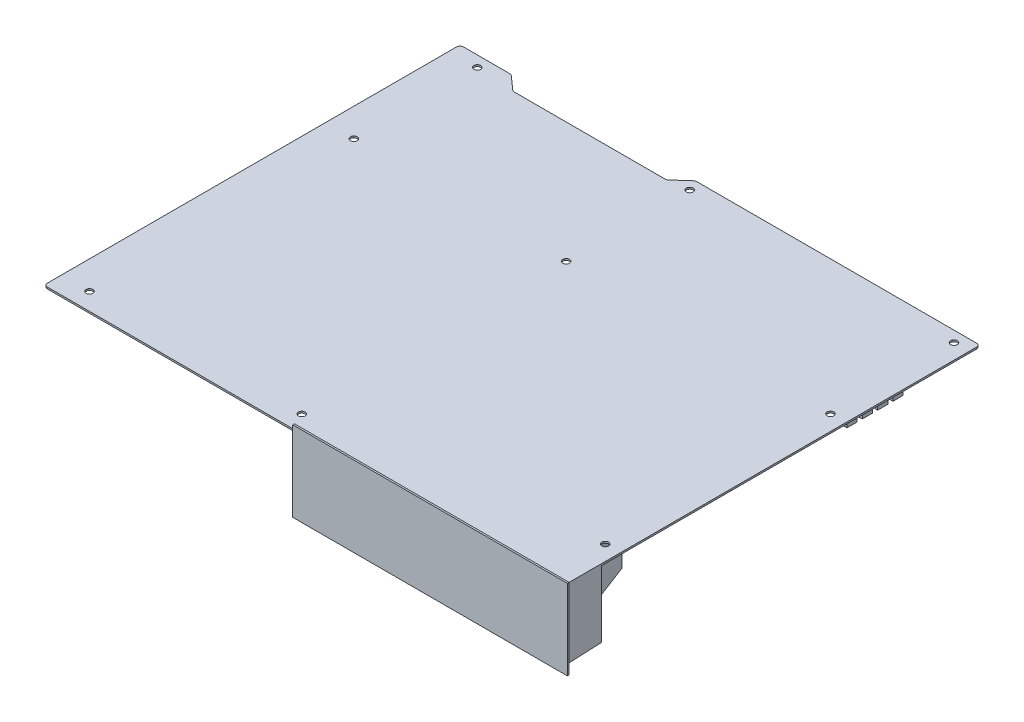
SolidWorks part; units mm, degrees
ref_plane "Front" through (0, 0, 0) normal (0, 0, 1) x (1, 0, 0)
ref_plane "Top" through (0, 0, 0) normal (0, 1, 0) x (1, 0, 0)
ref_plane "Right" through (0, 0, 0) normal (1, 0, 0) x (0, 0, -1)
sketch "Sketch1" plane through (0, 0, 0) normal (0, 1, 0) x (1, 0, 0)
  line L0 (-122.4, 121.92) -> (-122.4, 113.92) construction
  line L2 (-152.4, 121.92) -> (-152.4, -121.92)
  line L3 (-152.4, -121.92) -> (152.4, -121.92)
  line L4 (152.4, 121.92) -> (152.4, -121.92)
  line L7 (-122.4, 113.92) -> (-14.4, 113.92) construction
  line L8 (-14.4, 113.92) -> (-14.4, 121.92) construction
  line L9 (-152.4, 121.92) -> (-122.4, 121.92)
  line L10 (-14.4, 121.92) -> (152.4, 121.92)
  line L11 (-113.4, 113.92) -> (-23.4, 113.92)
  line L12 (-113.4, 113.92) -> (-122.4, 121.92)
  line L13 (-23.4, 113.92) -> (-14.4, 121.92)
  line L14 (-152.4, -111.76) -> (152.4, -111.76) construction
  line L15 (-152.4, 43.18) -> (152.4, 43.18) construction
  line L16 (-152.4, 115.57) -> (152.4, 115.57) construction
  line L17 (-135.89, -121.92) -> (-135.89, 121.92) construction
  line L18 (-11.43, -121.92) -> (-11.43, 115.57) construction
  line L19 (143.51, -121.92) -> (143.51, 121.92) construction
  circle A0 centre (-11.43, -111.76) radius 1.9812
  circle A1 centre (143.51, -88.9) radius 1.9812
  circle A2 centre (-135.89, 43.18) radius 1.9812
  circle A3 centre (-11.43, 115.57) radius 1.9812
  circle A4 centre (-135.89, 115.57) radius 1.9812
  circle A5 centre (143.51, 115.57) radius 1.9812
  circle A6 centre (-135.89, -111.76) radius 1.9812
  circle A7 centre (143.51, 43.18) radius 1.9812
  circle A8 centre (-11.43, 43.18) radius 1.9812
  point P0 (0, 0)
  point P12 (-68.4, 113.92)
  point P13 (-68.4, 113.92)
  dimension "D13" = 3.9624
  dimension "D1" = 304.8
  dimension "D2" = 243.84
  dimension "D3" = 30
  dimension "D4" = 108
  dimension "D5" = 90
  dimension "D6" = 8
  dimension "D7" = 227.33
  dimension "D8" = 10.16
  dimension "D9" = 154.94
  dimension "D10" = 124.46
  dimension "D11" = 279.4
  dimension "D12" = 16.51
  dimension "D14" = 22.86
extrude "Boss-Extrude1" add sketch "Sketch1" along normal blind 1
fillet "Fillet1" radius 2 4 edges at (-14.4, 0.5, -121.92) (-23.4, 0.5, -113.92) (-122.4, 0.5, -121.92) (-113.4, 0.5, -113.92)
fillet "Fillet2" radius 2 3 edges at (-152.4, 0.5, 121.92) (152.4, 0.5, -121.92) (-152.4, 0.5, -121.92)
sketch "Sketch2" plane through (0, 0, 0) normal (0, -1, 0) x (1, 0, 0)
  line L0 (152.4, 121.92) -> (152.4, -119.92) construction
  line L1 (-2.6, 121.92) -> (152.4, 121.92)
  line L2 (-2.6, 121.92) -> (-2.6, 99.92)
  line L4 (152.4, 121.92) -> (152.4, 99.92)
  line L5 (152.4, 99.92) -> (134.32, 91.3694)
  line L6 (134.32, 91.3694) -> (122.5293, 57.92)
  line L7 (-150.4, 121.92) -> (152.4, 121.92) construction
  line L8 (24.5293, 57.92) -> (122.5293, 57.92)
  line L9 (-2.6, 99.92) -> (24.5293, 57.92)
  dimension "D1" = 155
  dimension "D2" = 22
  dimension "D3" = 98
  dimension "D4" = 50
  dimension "D5" = 20
  dimension "D6" = 64
extrude "Boss-Extrude2" add sketch "Sketch2" along normal blind 40
sketch "Sketch3" plane through (0, 0, 121.92) normal (0, 0, 1) x (1, 0, 0)
  line L0 (152.4, -40) -> (-2.6, -40) construction
  line L1 (155.4, -43) -> (-5.6, -43)
  line L2 (155.4, -43) -> (155.4, 4)
  line L3 (155.4, 4) -> (-5.6, 4)
  line L4 (-5.6, -43) -> (-5.6, 4)
  line L5 (-150.4, 1) -> (152.4, 1) construction
  line L6 (152.4, 1) -> (152.4, -40) construction
  line L7 (-2.6, -40) -> (-2.6, 0) construction
  dimension "D1" = 3
  dimension "D2" = 3
  dimension "D3" = 3
  dimension "D4" = 3
extrude "Boss-Extrude3" add sketch "Sketch3" along normal blind 1
sketch "Sketch4" plane through (0, 0, 0) normal (1, 0, 0) x (0, 0, -1)
  line L2 (-55.6754, -37) -> (-121.92, -40)
  line L5 (-55.6754, -37) -> (-55.6754, -43.769)
  line L6 (-55.6754, -43.769) -> (-121.92, -43.769)
  line L7 (-121.92, -43.769) -> (-121.92, -40)
extrude "Cut-Extrude1" cut sketch "Sketch4" along normal mid plane 450
sketch "Sketch5" plane through (0, 0, 0) normal (0, -1, 0) x (1, 0, 0)
  line L0 (150.4, -121.92) -> (-13.6396, -121.92) construction
  line L1 (-2.6, -85.92) -> (137.4, -85.92)
  line L2 (-2.6, -85.92) -> (-2.6, -91.92)
  line L3 (-2.6, -91.92) -> (137.4, -91.92)
  line L4 (137.4, -85.92) -> (137.4, -91.92)
  line L5 (152.4, 99.92) -> (152.4, -119.92) construction
  dimension "D1" = 140
  dimension "D2" = 30
  dimension "D3" = 15
  dimension "D4" = 6
extrude "Boss-Extrude4" add sketch "Sketch5" along normal blind 5
sketch "Sketch6" plane through (0, -5, 0) normal (0, -1, 0) x (1, 0, 0)
  line L0 (-2.6, -91.92) -> (137.4, -91.92) construction
  line L1 (137.4, -85.92) -> (131.4, -85.92)
  line L2 (137.4, -85.92) -> (137.4, -91.92)
  line L3 (137.4, -91.92) -> (131.4, -91.92)
  line L4 (131.4, -85.92) -> (131.4, -91.92)
  line L6 (-2.6, -85.92) -> (3.4, -85.92)
  line L7 (-2.6, -85.92) -> (-2.6, -91.92)
  line L8 (-2.6, -91.92) -> (3.4, -91.92)
  line L9 (3.4, -85.92) -> (3.4, -91.92)
  dimension "D1" = 6
  dimension "D2" = 6
extrude "Boss-Extrude5" add sketch "Sketch6" along normal blind 12
sketch "Sketch7" plane through (0, -17, 0) normal (0, -1, 0) x (1, 0, 0)
  line L1 (-0.1, -88.17) -> (134.9, -88.17)
  line L2 (-0.1, -88.17) -> (-0.1, -89.67)
  line L3 (-0.1, -89.67) -> (134.9, -89.67)
  line L4 (134.9, -88.17) -> (134.9, -89.67)
  line L6 (137.4, -85.92) -> (-2.6, -85.92) construction
  line L8 (137.4, -91.92) -> (137.4, -85.92) construction
  dimension "D1" = 1.5
  dimension "D2" = 2.25
  dimension "D3" = 135
  dimension "D4" = 2.5
extrude "Cut-Extrude2" cut sketch "Sketch7" against normal blind 15
pattern_linear "LPattern2" count 4 spacing 9 along (0, 0, 1) of "Boss-Extrude5", "Cut-Extrude2", "Boss-Extrude4"
sketch "Sketch8" plane through (0, 0, 0) normal (0, -1, 0) x (1, 0, 0)
  line L0 (-152.4, -119.92) -> (-152.4, 119.92) construction
  line L1 (-35.4, 101.3981) -> (-29.4, 101.3981)
  line L2 (-35.4, 101.3981) -> (-35.4, 12.3981)
  line L3 (-35.4, 12.3981) -> (-29.4, 12.3981)
  line L4 (-29.4, 101.3981) -> (-29.4, 12.3981)
  line L6 (-33.4, 99.3981) -> (-31.4, 99.3981)
  line L7 (-33.4, 99.3981) -> (-33.4, 14.3981)
  line L8 (-33.4, 14.3981) -> (-31.4, 14.3981)
  line L9 (-31.4, 99.3981) -> (-31.4, 14.3981)
  dimension "D1" = 117
  dimension "D2" = 6
  dimension "D3" = 89
  dimension "D4" = 2
  dimension "D5" = 2
  dimension "D6" = 85
  dimension "D7" = 2
extrude "Boss-Extrude6" add sketch "Sketch8" along normal blind 12
sketch "Sketch9" plane through (0, 0, 0) normal (0, -1, 0) x (1, 0, 0)
  line L0 (150.4, -121.92) -> (-13.6396, -121.92) construction
  line L1 (37.4, 21.08) -> (72.4, 21.08)
  line L2 (37.4, 21.08) -> (37.4, -8.92)
  line L3 (37.4, -8.92) -> (72.4, -8.92)
  line L4 (72.4, 21.08) -> (72.4, -8.92)
  line L5 (152.4, 99.92) -> (152.4, -119.92) construction
  dimension "D1" = 113
  dimension "D2" = 30
  dimension "D3" = 35
  dimension "D4" = 80
extrude "Boss-Extrude7" add sketch "Sketch9" along normal blind 4
